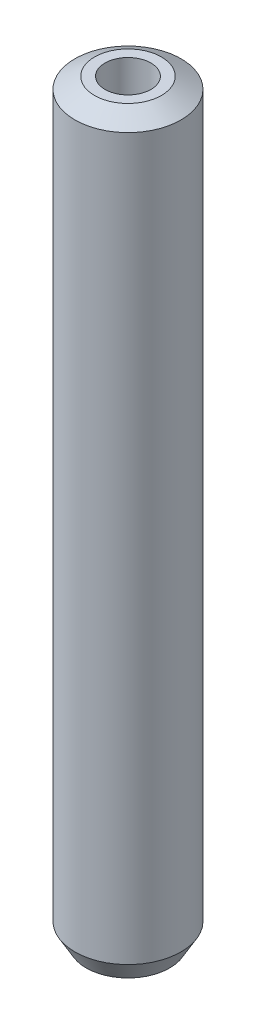
SolidWorks part; units mm, degrees
ref_plane "Front Plane" through (0, 0, 0) normal (0, 0, 1) x (1, 0, 0)
ref_plane "Top Plane" through (0, 0, 0) normal (0, 1, 0) x (1, 0, 0)
ref_plane "Right Plane" through (0, 0, 0) normal (1, 0, 0) x (0, 0, -1)
sketch "Sketch1" plane through (0, 0, 0) normal (0, 1, 0) x (1, 0, 0)
  circle A0 centre (0, 0) radius 15
  dimension "SHAFT_OD" = 30
extrude "Boss-Extrude1" add sketch "Sketch1" along normal blind 212.4848
sketch "Sketch2" plane through (0, 0, 0) normal (0, 1, 0) x (1, 0, 0)
  circle A0 centre (0, 0) radius 6.49
  dimension "BORE_D" = 12.9799
extrude "Cut-Extrude1" cut sketch "Sketch2" along normal through all
chamfer "Chamfer1" distance 3.2055 angle 60 2 edges at (0, 212.4848, 15) (0, 0, 15) first distance on face at (0, 212.4848, 15) first distance on face at (0, 0, 6.49)
